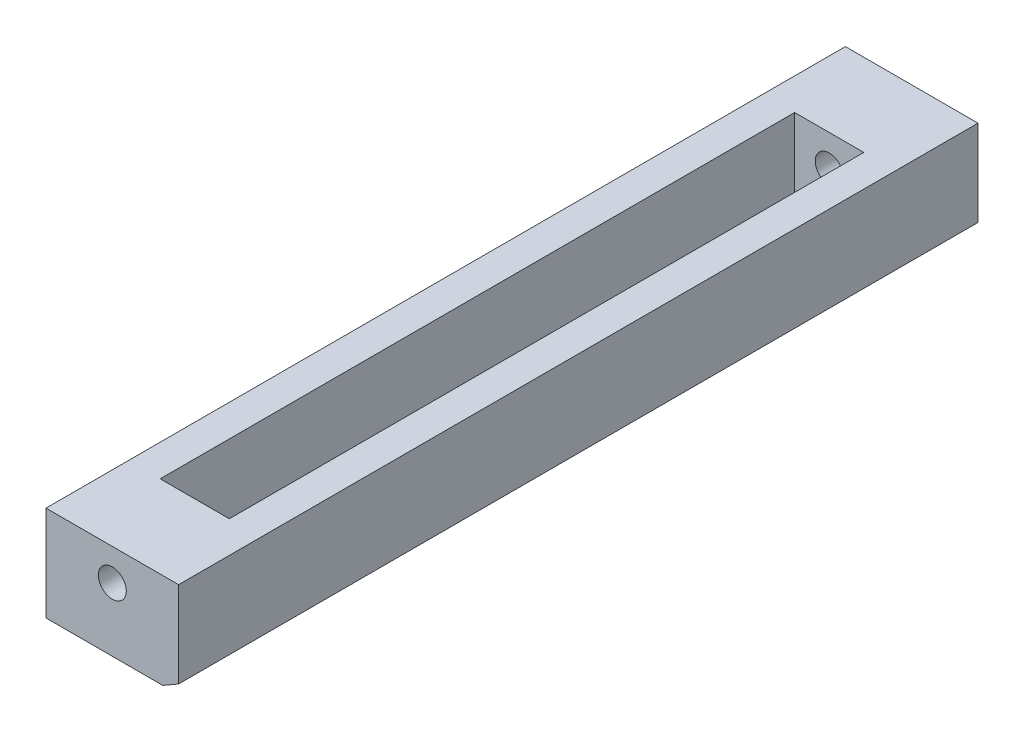
SolidWorks part; units mm, degrees
ref_plane "Front Plane" through (0, 0, 0) normal (0, 0, 1) x (1, 0, 0)
ref_plane "Top Plane" through (0, 0, 0) normal (0, 1, 0) x (1, 0, 0)
ref_plane "Right Plane" through (0, 0, 0) normal (1, 0, 0) x (0, 0, -1)
sketch "Sketch1" plane through (0, 0, 0) normal (0, 1, 0) x (1, 0, 0)
  line L1 (-6.6357, -40) -> (6.6358, -40)
  line L2 (-6.6357, -40) -> (-6.6357, 40)
  line L3 (-6.6357, 40) -> (6.6358, 40)
  line L4 (6.6358, -40) -> (6.6358, 40)
  line L5 (-6.6357, -40) -> (6.6358, 40) construction
  line L6 (-6.6357, 40) -> (6.6358, -40) construction
  line L11 (-3.4607, -31.75) -> (3.4608, -31.75)
  line L12 (-3.4607, -31.75) -> (-3.4607, 31.75)
  line L13 (-3.4607, 31.75) -> (3.4608, 31.75)
  line L14 (3.4608, -31.75) -> (3.4608, 31.75)
  line L15 (-3.4607, -31.75) -> (3.4608, 31.75) construction
  line L16 (-3.4607, 31.75) -> (3.4608, -31.75) construction
  point P0 (0, 0)
  point P6 (0, 0)
  dimension "D1" = 13.2715
  dimension "D2" = 80
  dimension "D3" = 3.175
  dimension "D4" = 63.5
extrude "Boss-Extrude1" add sketch "Sketch1" along normal blind 3.175 and the other way blind 6.35
sketch "Sketch4" plane through (0, 0, 40) normal (0, 0, 1) x (1, 0, 0)
  circle A0 centre (0, 0) radius 1.4
  dimension "D1" = 2.8
extrude "Cut-Extrude1" cut sketch "Sketch4" against normal through all
chamfer "Chamfer1" distance 1.5875 angle 30 1 edges at (6.6358, -6.35, 0) first distance on face at (0, -6.35, 0)
equation "\"tighttol\" = 0.005in"
equation "\"normtol\" = 0.01in"
equation "\"loosetol\" = 0.02in"
equation "\"Fry height\"= 0.5in"
equation "\"Fry spacing\"= 0.5625in"
equation "\"Potato width\"= \"Fry spacing\" * 4"
equation "\"Potato length\"= 80mm"
equation "\"D1@Sketch1\"=\"Fry spacing\" - 2 * \"loosetol\""
equation "\"D2@Sketch1\"=\"Potato length\""
equation "\"D1@Sketch4\"=2.8mm"
